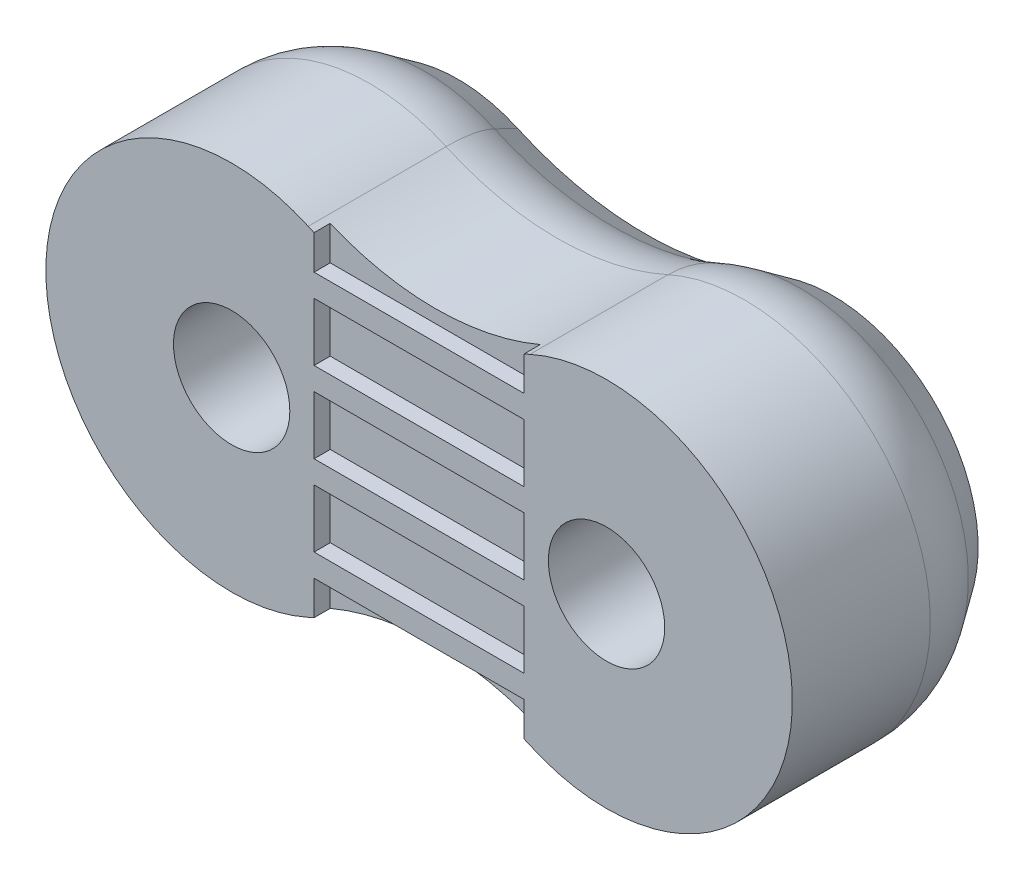
SolidWorks part; units mm, degrees
ref_plane "Front Plane" through (0, 0, 0) normal (0, 0, 1) x (1, 0, 0)
ref_plane "Top Plane" through (0, 0, 0) normal (0, 1, 0) x (1, 0, 0)
ref_plane "Right Plane" through (0, 0, 0) normal (1, 0, 0) x (0, 0, -1)
sketch "Sketch1" plane through (0, 0, 0) normal (0, 0, 1) x (1, 0, 0)
  line L0 (0.9795, 4) -> (17.6447, 4) construction
  line L1 (0.9795, -5) -> (18.5077, -5) construction
  arc A0 (6.6316, -5.7396) -> (-0.2316, -5.7396) centre (3.2, -13.331) ccw
  arc A1 (-0.2316, 4.7396) -> (6.6316, 4.7396) centre (3.2, 12.331) ccw
  arc A10 (-0.2316, 4.7396) -> (-0.2316, -5.7396) centre (-2.6, -0.5) ccw
  arc A12 (6.6316, -5.7396) -> (6.6316, 4.7396) centre (9, -0.5) ccw
extrude "Boss-Extrude1" add sketch "Sketch1" against normal blind 7
sketch "Sketch5" plane through (0, 0, 0) normal (0, 0, 1) x (1, 0, 0)
  circle A1 centre (9, -0.5) radius 1.8
  circle A3 centre (-2.6, -0.5) radius 1.8
extrude "Cut-Extrude4" cut sketch "Sketch5" against normal through all
sketch "Sketch2" plane through (0, 0, 0) normal (0, 0, 1) x (1, 0, 0)
  line L0 (-0.05, 2.9) -> (-0.05, 1.1)
  line L2 (-0.05, 0.4) -> (-0.05, -1.4)
  line L3 (6.45, -4.6) -> (-0.05, -4.6)
  line L4 (6.45, -2.1) -> (-0.05, -2.1)
  line L5 (-0.05, -2.1) -> (-0.05, -3.9)
  line L6 (-0.05, -3.9) -> (6.45, -3.9)
  line L7 (-0.05, -4.6) -> (-0.05, -5.6601)
  line L8 (6.45, 0.4) -> (-0.05, 0.4)
  line L9 (6.45, -3.9) -> (6.45, -2.1)
  line L10 (-0.05, -1.4) -> (6.45, -1.4)
  line L11 (6.45, -1.4) -> (6.45, 0.4)
  line L12 (6.45, 2.9) -> (-0.05, 2.9)
  line L13 (6.45, 1.1) -> (6.45, 2.9)
  line L14 (-0.05, 1.1) -> (6.45, 1.1)
  line L15 (6.45, 3.6) -> (6.45, 4.6601)
  line L18 (-0.05, 3.6) -> (6.45, 3.6)
  line L23 (6.45, -5.6601) -> (6.45, -4.6)
  line L26 (-0.05, 4.6601) -> (-0.05, 3.6)
  arc A0 (-0.2316, 4.7396) -> (6.6316, 4.7396) centre (3.2, 12.331) ccw construction
  arc A1 (-0.05, 4.6601) -> (6.45, 4.6601) centre (3.2, 12.331) ccw
  arc A2 (6.6316, -5.7396) -> (-0.2316, -5.7396) centre (3.2, -13.331) ccw construction
  arc A3 (6.45, -5.6601) -> (-0.05, -5.6601) centre (3.2, -13.331) ccw
extrude "Cut-Extrude1" cut sketch "Sketch2" against normal blind 0.5
sketch "Sketch6" plane through (0, 0, -7) normal (0, 0, -1) x (-1, 0, 0)
  line L1 (-0.9796, -0.5) -> (0.8102, -3.6)
  line L2 (0.8102, -3.6) -> (4.3898, -3.6)
  line L3 (4.3898, -3.6) -> (6.1796, -0.5)
  line L4 (6.1796, -0.5) -> (4.3898, 2.6)
  line L5 (4.3898, 2.6) -> (0.8102, 2.6)
  line L6 (0.8102, 2.6) -> (-0.9796, -0.5)
  line L7 (-5.4204, -0.5) -> (-7.2102, 2.6)
  line L8 (-7.2102, 2.6) -> (-10.7898, 2.6)
  line L9 (-10.7898, 2.6) -> (-12.5796, -0.5)
  line L10 (-12.5796, -0.5) -> (-10.7898, -3.6)
  line L11 (-10.7898, -3.6) -> (-7.2102, -3.6)
  line L12 (-7.2102, -3.6) -> (-5.4204, -0.5)
  circle A0 centre (2.6, -0.5) radius 3.1 construction
  circle A1 centre (-9, -0.5) radius 3.1 construction
extrude "Cut-Extrude5" cut sketch "Sketch6" against normal blind 2.5
chamfer "Chamfer1" distance 1.25 angle 55 4 edges at (14.75, -0.5, -7) (3.2, 4, -7) (3.2, -5, -7) (-8.35, -0.5, -7) first distance on face at (9, -0.5, -7)
fillet "Fillet1" radius 3 4 edges at (3.2, 4, -5.2148) (14.75, -0.5, -5.2148) (3.2, -5, -5.2148) (-8.35, -0.5, -5.2148)
sketch "Sketch7" plane through (0, 0, -4.5) normal (0, 0, -1) x (-1, 0, 0)
  circle A0 centre (-9, -0.5) radius 1.8 construction
  circle A1 centre (2.6, -0.5) radius 1.8 construction
  circle A2 centre (-9, -0.5) radius 1.8
  circle A3 centre (2.6, -0.5) radius 1.8
extrude "Boss-Extrude2" add sketch "Sketch7" against normal blind 0.6
sketch "Sketch8" plane through (0, 0, -4.5) normal (0, 0, -1) x (-1, 0, 0)
  circle A4 centre (-9, -0.5) radius 1.4
  circle A5 centre (2.6, -0.5) radius 1.4
  circle A6 centre (-9, -0.5) radius 0.6
  circle A7 centre (2.6, -0.5) radius 0.6
  dimension "D3" = 0.8
  dimension "D4" = 0.8
extrude "Boss-Extrude3" add sketch "Sketch8" along normal up to surface (2.5 mm away) up to face at (3.2, -0.5, -7)
